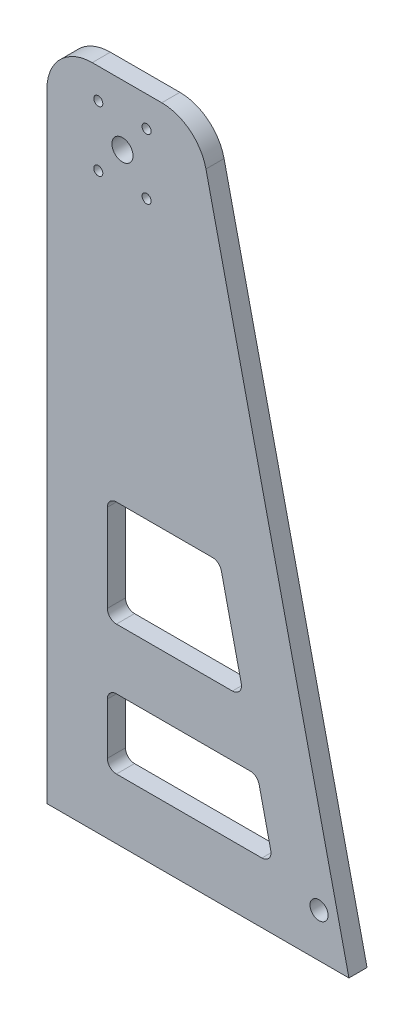
SolidWorks part; units mm, degrees
ref_plane "Plano frontal" through (0, 0, 0) normal (0, 0, 1) x (1, 0, 0)
ref_plane "Plano superior" through (0, 0, 0) normal (0, 1, 0) x (1, 0, 0)
ref_plane "Plano direito" through (0, 0, 0) normal (1, 0, 0) x (0, 0, -1)
sketch "Esboço1" plane through (0, 0, 0) normal (0, 0, 1) x (1, 0, 0)
  line L0 (0, 0) -> (0, 220)
  line L2 (100, 0) -> (0, 0)
  line L3 (0, 220) -> (50, 220)
  line L4 (50, 220) -> (100, 0)
  line L5 (10, 103) -> (10, 15) construction
  line L6 (25, 220) -> (25, 180) construction
  line L7 (10, 15) -> (75.8194, 15) construction
  line L8 (75.8194, 15) -> (55.8194, 103) construction
  line L9 (55.8194, 103) -> (10, 103) construction
  line L10 (20, 95) -> (20, 66)
  line L11 (23, 63) -> (61.4135, 63)
  line L12 (64.3389, 66.6649) -> (57.748, 95.6649)
  line L13 (54.8226, 98) -> (23, 98)
  line L14 (20, 40) -> (20, 23)
  line L15 (23, 20) -> (71.1862, 20)
  line L16 (74.1116, 23.6649) -> (70.248, 40.6649)
  line L17 (23, 43) -> (67.3226, 43)
  line L18 (17, 200) -> (33, 200) construction
  line L19 (17, 210) -> (33, 210) construction
  line L20 (17, 210) -> (17, 190) construction
  line L21 (17, 190) -> (33, 190) construction
  line L22 (33, 210) -> (33, 190) construction
  line L23 (17, 210) -> (33, 190) construction
  line L24 (17, 190) -> (33, 210) construction
  arc A8 (70.248, 40.6649) -> (67.3226, 43) centre (67.3226, 40) ccw
  arc A9 (71.1862, 20) -> (74.1116, 23.6649) centre (71.1862, 23) ccw
  arc A10 (20, 23) -> (23, 20) centre (23, 23) ccw
  arc A11 (20, 40) -> (23, 43) centre (23, 40) cw
  arc A12 (57.748, 95.6649) -> (54.8226, 98) centre (54.8226, 95) ccw
  arc A13 (61.4135, 63) -> (64.3389, 66.6649) centre (61.4135, 66) ccw
  arc A14 (20, 66) -> (23, 63) centre (23, 66) ccw
  arc A15 (20, 95) -> (23, 98) centre (23, 95) cw
  circle A16 centre (17, 210) radius 1.5
  circle A17 centre (33, 210) radius 1.5
  circle A18 centre (33, 190) radius 1.5
  circle A19 centre (17, 190) radius 1.5
  circle A20 centre (25, 200) radius 3.5
  point P8 (25, 200)
  point P49 (20, 63)
  dimension "D3" = 20
  dimension "D4" = 16
  dimension "D6" = 3
  dimension "D7" = 7
  dimension "D21" = 3
  dimension "D1" = 220
  dimension "D2" = 100
  dimension "D5" = 50
  dimension "D9" = 20
  dimension "D10" = 20
  dimension "D11" = 10
  dimension "D12" = 20
  dimension "D13" = 15
  dimension "D14" = 20
  dimension "D15" = 10
  dimension "D16" = 29
  dimension "D17" = 17
  dimension "D18" = 10
  dimension "D8" = 20
extrude "Ressalto-extrusão2" add sketch "Esboço1" along normal blind 6
fillet "Filete1" radius 15 2 edges at (0, 220, 3) (50, 220, 3)
sketch "Esboço2" plane through (0, 0, 0) normal (0, 0, -1) x (-1, 0, 0)
  circle A0 centre (-90.0963, 14.5) radius 3
extrude "Corte-extrusão1" cut sketch "Esboço2" against normal blind 10
